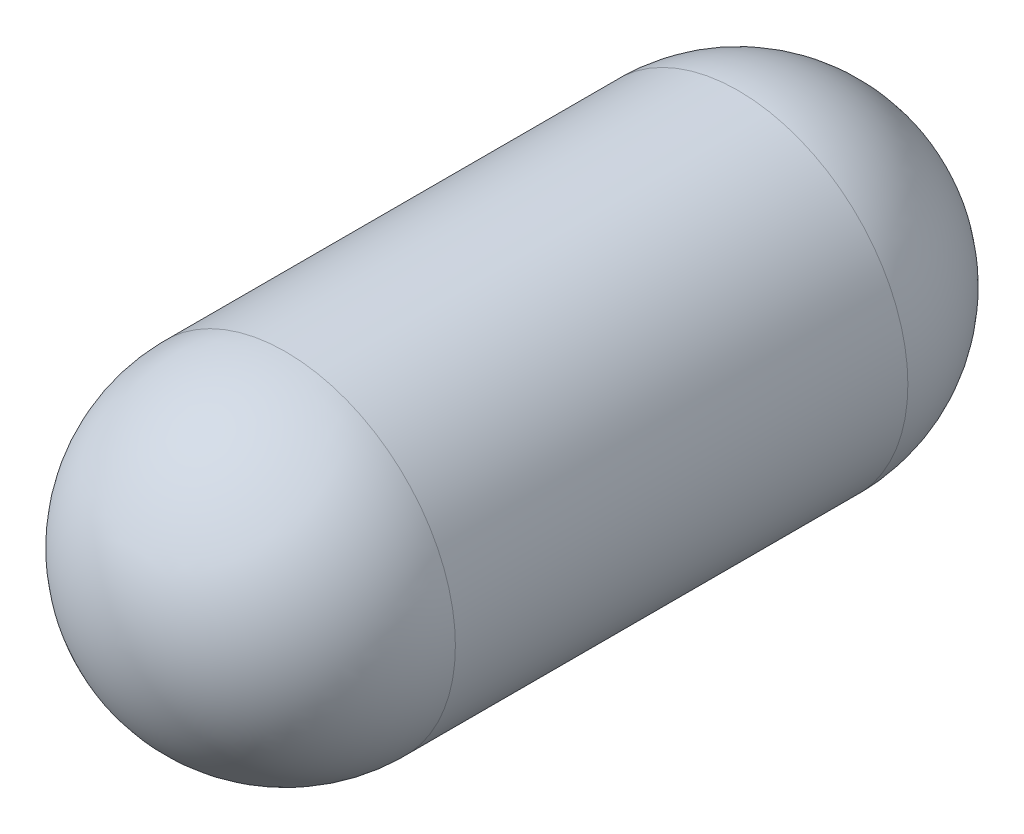
SolidWorks part; units mm, degrees
ref_plane "Front Plane" through (0, 0, 0) normal (0, 0, 1) x (1, 0, 0)
ref_plane "Top Plane" through (0, 0, 0) normal (0, 1, 0) x (1, 0, 0)
ref_plane "Right Plane" through (0, 0, 0) normal (1, 0, 0) x (0, 0, -1)
sketch "Sketch1" plane through (0, 0, 0) normal (0, 0, 1) x (1, 0, 0)
  circle A0 centre (0, 0) radius 9.525
  dimension "D1" = 19.05
extrude "Boss-Extrude1" add sketch "Sketch1" along normal blind 25.4
sketch "Sketch2" plane through (0, 0, 0) normal (1, 0, 0) x (0, 0, -1)
  line L0 (0, -9.525) -> (0, 9.525) construction
  line L1 (0, 9.525) -> (0, -9.525)
  arc A0 (0, 9.525) -> (0, -9.525) centre (0, 0) cw
revolve "Revolve1" add sketch "Sketch2" angle 360 about L1
sketch "Sketch3" plane through (0, 0, 0) normal (1, 0, 0) x (0, 0, -1)
  line L0 (-25.4, 9.525) -> (-25.4, -9.525) construction
  line L1 (-25.4, 9.525) -> (-25.4, -9.525)
  arc A0 (-25.4, 9.525) -> (-25.4, -9.525) centre (-25.4, 0) ccw
revolve "Revolve2" add sketch "Sketch3" angle 360 about L1
ref_plane "Plane1" through (0, 0, 25.4) normal (0, 0, 1) x (1, 0, 0)
sketch "Sketch6" plane through (0, 0, 25.4) normal (0, 0, 1) x (1, 0, 0)
  point P0 (0, 0)
ref_plane "Plane2" through (0, 0, 0) normal (0, 0, 1) x (1, 0, 0)
sketch "Sketch7" plane through (0, 0, 0) normal (0, 0, 1) x (1, 0, 0)
  point P0 (0, 0)
sketch3d "3DSketch1"
  line L0 (0, 0, 0) -> (0, 0, 25.4)
